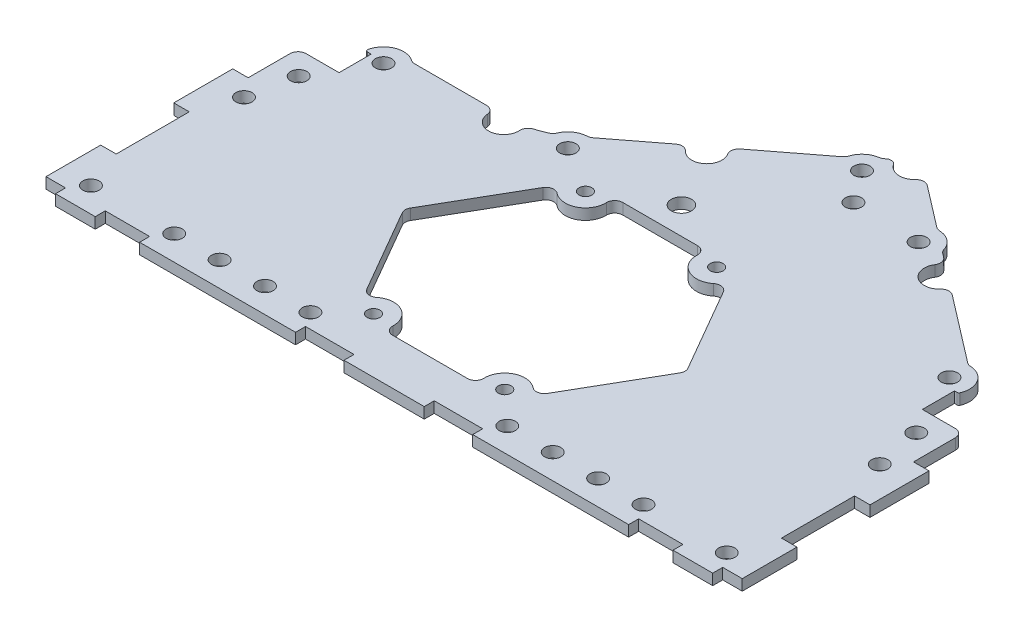
SolidWorks part; units mm, degrees
material "AISI 1020 Steel, Cold Rolled"
ref_plane "Front Plane" through (0, 0, 0) normal (0, 0, 1) x (1, 0, 0)
ref_plane "Top Plane" through (0, 0, 0) normal (0, 1, 0) x (1, 0, 0)
ref_plane "Right Plane" through (0, 0, 0) normal (1, 0, 0) x (0, 0, -1)
sketch "Top Layout" plane through (0, 0, 0) normal (0, 1, 0) x (1, 0, 0)
  line L0 (-114.046, -123.825) -> (-104.775, -123.825) construction
  line L1 (-104.775, -142.875) -> (-101.6, -142.875)
  line L2 (-104.775, -142.875) -> (-104.775, -104.775)
  line L3 (-104.775, -104.775) -> (-101.6, -104.775)
  line L4 (-101.6, -142.875) -> (-101.6, -104.775)
  line L5 (-104.775, -142.875) -> (-101.6, -104.775) construction
  line L6 (-104.775, -104.775) -> (-101.6, -142.875) construction
  line L7 (-19.05, -105.8164) -> (-101.6, -105.8164)
  line L8 (-19.05, -105.8164) -> (-19.05, -141.8336)
  line L9 (-19.05, -141.8336) -> (-101.6, -141.8336)
  line L10 (-101.6, -105.8164) -> (-101.6, -141.8336)
  line L11 (-19.05, -105.8164) -> (-101.6, -141.8336) construction
  line L12 (-19.05, -141.8336) -> (-101.6, -105.8164) construction
  line L13 (-133.096, -85.725) -> (-114.046, -85.725)
  line L14 (-133.096, -85.725) -> (-133.096, -161.925)
  line L15 (-133.096, -161.925) -> (-114.046, -161.925)
  line L16 (-114.046, -85.725) -> (-114.046, -161.925)
  line L17 (-133.096, -85.725) -> (-114.046, -161.925) construction
  line L18 (-133.096, -161.925) -> (-114.046, -85.725) construction
  line L19 (-104.775, -123.825) -> (0, -123.825) construction
  line L20 (0, -123.825) -> (0, 0) construction
  line L21 (-52.3528, -40.1717) -> (0, 0) construction
  line L22 (-70.6449, -16.3328) -> (-18.2922, 23.8388)
  line L23 (-34.0606, -64.0105) -> (18.2922, -23.8388)
  line L24 (-30.9251, 40.3023) -> (-122.2248, -29.7544)
  line L25 (-153.9748, -53.975) -> (-153.9748, -123.825)
  line L26 (-109.5248, -162.052) -> (109.5248, -162.052)
  line L27 (0, -162.052) -> (0, -123.825) construction
  line L28 (-109.5248, -162.052) -> (-109.5248, -20.0093) construction
  line L29 (-104.775, -142.875) -> (-104.775, -152.527)
  line L30 (-104.775, -152.527) -> (104.775, -152.527)
  line L31 (104.775, -104.775) -> (101.6, -104.775)
  line L32 (-144.4498, -73.025) -> (-109.5248, -73.025)
  line L33 (-144.4498, -73.025) -> (-144.4498, -123.825)
  line L34 (-144.4498, -123.825) -> (-109.5248, -123.825) construction
  line L35 (-109.5248, -73.025) -> (-109.5248, -162.052)
  line L36 (-144.4498, -73.025) -> (-109.5248, -123.825) construction
  line L37 (-144.4498, -123.825) -> (-109.5248, -73.025) construction
  line L38 (101.6, -142.875) -> (101.6, -104.775)
  line L39 (104.775, -142.875) -> (101.6, -142.875)
  line L40 (104.775, -142.875) -> (104.775, -104.775)
  line L41 (104.775, -142.875) -> (104.775, -152.527)
  line L42 (109.5248, -162.052) -> (109.5248, -20.0093) construction
  line L43 (30.9251, 40.3023) -> (122.2248, -29.7544)
  line L45 (19.05, -141.8336) -> (101.6, -141.8336)
  line L46 (101.6, -105.8164) -> (101.6, -141.8336)
  line L47 (19.05, -105.8164) -> (101.6, -105.8164)
  line L48 (19.05, -105.8164) -> (19.05, -141.8336)
  line L49 (133.096, -161.925) -> (114.046, -161.925)
  line L50 (114.046, -85.725) -> (114.046, -161.925)
  line L51 (133.096, -85.725) -> (114.046, -85.725)
  line L52 (133.096, -85.725) -> (133.096, -161.925)
  line L53 (144.4498, -123.825) -> (109.5248, -123.825) construction
  line L54 (109.5248, -73.025) -> (109.5248, -162.052)
  line L55 (144.4498, -73.025) -> (109.5248, -73.025)
  line L56 (144.4498, -73.025) -> (144.4498, -123.825)
  line L57 (-109.5248, -123.825) -> (-109.5248, -162.052) construction
  line L62 (-153.9748, -53.975) -> (-122.2248, -53.975)
  line L63 (-122.2248, -53.975) -> (-122.2248, -29.7544)
  line L64 (-144.4498, -123.825) -> (-153.9748, -123.825)
  line L65 (153.9748, -53.975) -> (153.9748, -123.825)
  line L66 (109.5248, -123.825) -> (109.5248, -162.052) construction
  line L67 (144.4498, -123.825) -> (153.9748, -123.825)
  line L68 (122.2248, -29.7544) -> (122.2248, -53.975)
  line L73 (-104.775, -104.775) -> (-104.775, -16.3647) construction
  line L74 (-95.25, -162.052) -> (-95.25, -9.0559) construction
  line L75 (-109.5248, -162.052) -> (-109.5248, -123.825) construction
  line L76 (109.5248, -162.052) -> (109.5248, -123.825) construction
  line L77 (122.2248, -53.975) -> (153.9748, -53.975)
  line L83 (104.775, -155.5496) -> (-104.775, -155.5496) construction
  line L88 (95.25, -162.052) -> (95.25, -9.0559) construction
  line L89 (104.775, -104.775) -> (104.775, -16.3647) construction
  line L92 (-104.775, -152.527) -> (-104.775, -162.052) construction
  line L93 (-14.605, -76.327) -> (14.605, -76.327)
  line L94 (-14.605, -76.327) -> (-14.605, -152.527)
  line L95 (-14.605, -152.527) -> (14.605, -152.527)
  line L96 (14.605, -76.327) -> (14.605, -152.527)
  line L97 (-14.605, -76.327) -> (14.605, -152.527) construction
  line L98 (-14.605, -152.527) -> (14.605, -76.327) construction
  line L99 (104.775, -152.527) -> (104.775, -162.052) construction
  line L100 (-19.05, -105.8164) -> (0, -105.8164) construction
  line L107 (0, -105.8164) -> (19.05, -105.8164) construction
  line L108 (104.775, -123.825) -> (114.046, -123.825) construction
  circle A0 centre (0, 0) radius 114.3
  circle A1 centre (0, 0) radius 6.35
  circle A2 centre (-52.3528, -40.1717) radius 17.8
  circle A3 centre (0, 0) radius 30.0482
  circle A4 centre (-52.3528, -40.1717) radius 30.0482
  arc A5 (-30.9251, 40.3023) -> (30.9251, 40.3023) centre (0, 0) cw
  point P2 (-103.1875, -123.825)
  point P7 (-60.325, -123.825)
  point P12 (-123.571, -123.825)
  point P30 (-126.9873, -98.425)
  point P35 (0, -114.427)
  point P53 (0, -152.527)
  dimension "D1" = 35.6
  dimension "D2" = 12.7
  dimension "D3" = 228.6
  dimension "D11" = 60.0964
  dimension "D12" = 50.8
  dimension "D14" = 52.5
  dimension "D4" = 3.175
  dimension "D5" = 19.05
  dimension "D6" = 76.2
  dimension "D7" = 82.55
  dimension "D8" = 38.1
  dimension "D9" = 104.775
  dimension "D10" = 18.0086
  dimension "D13" = 9.525
  dimension "D15" = 4.7498
  dimension "D16" = 9.525
  dimension "D17" = 9.652
  dimension "D18" = 50.8
  dimension "D19" = 12.446
  dimension "D20" = 65.9892
  dimension "D21" = 19.05
  dimension "D22" = 34.925
  dimension "D23" = 123.825
  dimension "D24" = 12.7
  dimension "D25" = 9.525
  dimension "D26" = 29.21
  dimension "D27" = 76.2
  dimension "D28" = 3.0226
sketch "Side Layout" plane through (0, 0, 0) normal (1, 0, 0) x (0, 0, -1)
  line L0 (0, -38.1) -> (0, 33.7344) construction
  line L1 (-114.3, -20.955) -> (114.3, -20.955)
  line L2 (-114.3, -20.955) -> (-114.3, -33.655)
  line L3 (-114.3, -33.655) -> (114.3, -33.655)
  line L4 (114.3, -20.955) -> (114.3, -33.655)
  line L5 (-114.3, -20.955) -> (114.3, -33.655) construction
  line L6 (-114.3, -33.655) -> (114.3, -20.955) construction
  line L7 (-9.525, -32.9406) -> (9.525, -32.9406)
  line L8 (-9.525, -32.9406) -> (-9.525, -38.1)
  line L9 (-9.525, -38.1) -> (9.525, -38.1)
  line L10 (9.525, -32.9406) -> (9.525, -38.1)
  line L11 (-9.525, -32.9406) -> (9.525, -38.1) construction
  line L12 (-9.525, -38.1) -> (9.525, -32.9406) construction
  line L13 (-11.9126, -29.3338) -> (11.9126, -29.3338)
  line L14 (-11.9126, -29.3338) -> (-11.9126, -32.9406)
  line L15 (-11.9126, -32.9406) -> (11.9126, -32.9406)
  line L16 (11.9126, -29.3338) -> (11.9126, -32.9406)
  line L17 (-11.9126, -29.3338) -> (11.9126, -32.9406) construction
  line L18 (-11.9126, -32.9406) -> (11.9126, -29.3338) construction
  line L19 (-6.35, -32.9406) -> (6.35, -32.9406)
  line L20 (-6.35, -32.9406) -> (-6.35, 33.7344)
  line L21 (-6.35, 33.7344) -> (6.35, 33.7344)
  line L22 (6.35, -32.9406) -> (6.35, 33.7344)
  line L23 (-6.35, -32.9406) -> (6.35, 33.7344) construction
  line L24 (-6.35, 33.7344) -> (6.35, -32.9406) construction
  line L25 (-162.052, 0) -> (-123.825, 0) construction
  line L26 (114.3, -33.655) -> (114.3, 0) construction
  line L27 (-142.875, 19.05) -> (-104.775, 19.05)
  line L28 (-40.1717, -9.525) -> (-40.1717, 5.4) construction
  line L29 (-142.875, 19.05) -> (-142.875, -19.05)
  line L30 (-142.875, -19.05) -> (-104.775, -19.05)
  line L31 (-104.775, 19.05) -> (-104.775, -19.05)
  line L32 (-142.875, 19.05) -> (-104.775, -19.05) construction
  line L33 (-142.875, -19.05) -> (-104.775, 19.05) construction
  line L34 (-130.175, -38.1) -> (-117.9516, -38.1) construction
  line L35 (-57.9717, -14.6) -> (-22.3717, -14.6)
  line L36 (-30.0482, -2.794) -> (30.0482, -2.794)
  line L37 (-30.0482, -2.794) -> (-30.0482, -20.955)
  line L38 (-30.0482, -20.955) -> (30.0482, -20.955)
  line L39 (30.0482, -2.794) -> (30.0482, -20.955)
  line L40 (-30.0482, -2.794) -> (30.0482, -20.955) construction
  line L41 (-30.0482, -20.955) -> (30.0482, -2.794) construction
  line L42 (-30.0482, -2.794) -> (-30.0482, 0) construction
  line L43 (-123.825, 0) -> (0, 0) construction
  line L44 (-57.9717, -14.6) -> (-57.9717, 25.4)
  line L45 (-57.9717, 25.4) -> (-22.3717, 25.4)
  line L46 (-22.3717, -14.6) -> (-22.3717, 25.4)
  line L47 (-19.05, 0) -> (19.05, 0)
  line L48 (-19.05, 0) -> (-19.05, -1.9812)
  line L49 (-19.05, -1.9812) -> (19.05, -1.9812)
  line L50 (19.05, 0) -> (19.05, -1.9812)
  line L51 (-19.05, 0) -> (19.05, -1.9812) construction
  line L52 (-19.05, -1.9812) -> (19.05, 0) construction
  line L53 (-70.2199, -3.175) -> (-10.1235, -3.175)
  line L54 (-70.2199, -3.175) -> (-70.2199, -15.875)
  line L55 (-70.2199, -15.875) -> (-10.1235, -15.875)
  line L56 (-10.1235, -3.175) -> (-10.1235, -15.875)
  line L57 (-70.2199, -3.175) -> (-10.1235, -15.875) construction
  line L58 (-70.2199, -15.875) -> (-10.1235, -3.175) construction
  line L59 (-40.1717, -9.525) -> (-40.1717, 0) construction
  line L60 (-57.9717, -14.6) -> (-22.3717, 25.4) construction
  line L61 (-57.9717, 25.4) -> (-22.3717, -14.6) construction
  line L62 (-22.3717, 0) -> (-57.9717, 0) construction
  line L63 (-137.8162, 0) -> (-123.825, -13.9912) construction
  line L64 (-139.065, 15.24) -> (-108.585, 15.24) construction
  line L65 (-139.065, 15.24) -> (-139.065, -15.24) construction
  line L66 (-139.065, -15.24) -> (-108.585, -15.24) construction
  line L67 (-108.585, 15.24) -> (-108.585, -15.24) construction
  line L68 (-139.065, 15.24) -> (-108.585, -15.24) construction
  line L69 (-139.065, -15.24) -> (-108.585, 15.24) construction
  line L70 (-137.8162, 0) -> (-123.825, 13.9912) construction
  line L71 (-123.825, -13.9912) -> (-109.8338, 0) construction
  line L72 (-123.825, 13.9912) -> (-109.8338, 0) construction
  line L73 (-137.8162, 0) -> (-109.8338, 0) construction
  line L74 (-123.825, -13.9912) -> (-123.825, 13.9912) construction
  line L75 (-6.35, 17.8594) -> (6.35, 17.8594)
  line L76 (114.3, 0) -> (-114.3, 0) construction
  line L77 (-22.3717, 19.05) -> (-6.35, 19.05) construction
  line L78 (-123.825, 38.1) -> (-97.9206, 38.1) construction
  line L79 (-19.05, -3.5814) -> (19.05, -3.5814)
  line L80 (-19.05, -3.5814) -> (-19.05, -1.9812)
  line L81 (-19.05, -1.9812) -> (19.05, -1.9812)
  line L82 (19.05, -3.5814) -> (19.05, -1.9812)
  line L83 (-19.05, -3.5814) -> (19.05, -1.9812) construction
  line L84 (-19.05, -1.9812) -> (19.05, -3.5814) construction
  line L85 (-8.7376, -16.7608) -> (8.7376, -16.7608)
  line L86 (-8.7376, -16.7608) -> (-8.7376, -29.3338)
  line L87 (-8.7376, -29.3338) -> (8.7376, -29.3338)
  line L88 (8.7376, -16.7608) -> (8.7376, -29.3338)
  line L89 (-8.7376, -16.7608) -> (8.7376, -29.3338) construction
  line L90 (-8.7376, -29.3338) -> (8.7376, -16.7608) construction
  line L91 (-8.7376, -3.5814) -> (8.7376, -3.5814)
  line L92 (-8.7376, -3.5814) -> (-8.7376, -16.1544)
  line L93 (-8.7376, -16.1544) -> (8.7376, -16.1544)
  line L94 (8.7376, -3.5814) -> (8.7376, -16.1544)
  line L95 (-8.7376, -3.5814) -> (8.7376, -16.1544) construction
  line L96 (-8.7376, -16.1544) -> (8.7376, -3.5814) construction
  circle A0 centre (-123.825, 0) radius 18.0086
  circle A1 centre (-123.825, 0) radius 38.1
  circle A2 centre (-139.065, 15.24) radius 1.905
  circle A3 centre (-108.585, 15.24) radius 1.905
  circle A4 centre (-108.585, -15.24) radius 1.905
  circle A5 centre (-139.065, -15.24) radius 1.905
  circle A6 centre (-137.8162, 0) radius 1.6002
  circle A7 centre (-123.825, 13.9912) radius 1.6002
  circle A8 centre (-109.8338, 0) radius 1.6002
  circle A9 centre (-123.825, -13.9912) radius 1.6002
  point P0 (0, -27.305)
  point P6 (0, -31.1372)
  point P7 (0, -35.5203)
  point P21 (0, 0.3969)
  point P32 (0, -11.8745)
  point P43 (0, -0.9906)
  point P55 (-40.1717, -9.525)
  point P72 (-40.1717, 5.4)
  point P88 (0, -23.0473)
  point P93 (0, -2.7813)
  point P102 (0, -9.8679)
  dimension "D17" = 3.81
  dimension "D18" = 3.2004
  dimension "D1" = 12.7
  dimension "D2" = 5.1594
  dimension "D3" = 19.05
  dimension "D4" = 3.6068
  dimension "D5" = 23.8252
  dimension "D6" = 12.7
  dimension "D7" = 18.161
  dimension "D8" = 1.9812
  dimension "D9" = 12.7
  dimension "D10" = 40
  dimension "D11" = 25.4
  dimension "D12" = 50.8
  dimension "D13" = 41.275
  dimension "D14" = 30.48
  dimension "D15" = 4.445
  dimension "D16" = 19.7866
  dimension "D19" = 15.875
  dimension "D20" = 6.35
  dimension "D21" = 38.1
  dimension "D22" = 1.6002
  dimension "D23" = 38.1
  dimension "D24" = 17.4752
  dimension "D25" = 12.573
ref_plane "Plane1" through (0, 25.4, 0) normal (0, 1, 0) x (1, 0, 0)
sketch "Sketch3" plane through (0, 25.4, 0) normal (0, 1, 0) x (1, 0, 0)
  line L0 (-104.775, -36.3747) -> (-30.9251, 20.2924)
  line L1 (-104.775, -104.775) -> (-104.775, -16.3647) construction
  line L2 (0, -200130.175) -> (0, 199882.0484) construction
  line L3 (-30.9251, 40.3023) -> (-122.2248, -29.7544) construction
  line L5 (-104.775, -36.3747) -> (-104.775, -77.6497)
  line L6 (-92.075, -77.6497) -> (-104.775, -77.6497)
  line L7 (30.9251, 20.2924) -> (104.775, -36.3747)
  line L8 (104.775, -77.6497) -> (92.075, -77.6497)
  line L9 (104.775, -36.3747) -> (104.775, -77.6497)
  line L11 (104.775, -104.775) -> (104.775, -16.3647) construction
  line L12 (30.9251, 40.3023) -> (122.2248, -29.7544) construction
  line L13 (92.075, -74.6536) -> (24.1423, -22.5271)
  line L14 (-32.2514, -66.3682) -> (20.1013, -26.1965)
  line L15 (-30.9251, 20.2924) -> (0, 44.022)
  line L16 (0, 44.022) -> (30.9251, 20.2924)
  line L17 (-92.075, -77.6497) -> (-92.075, -73.1917)
  line L19 (-92.075, -73.1917) -> (-52.3528, -73.1917)
  line L20 (92.075, -74.6536) -> (92.075, -77.6497)
  circle A0 centre (-52.3528, -40.1717) radius 17.8 construction
  circle A1 centre (-52.3528, -40.1717) radius 17.8
  circle A2 centre (0, 0) radius 6.35
  circle A3 centre (0, 0) radius 6.35 construction
  arc A4 (-52.3528, -73.1917) -> (-32.2514, -66.3682) centre (-52.3528, -40.1717) ccw
  arc A5 (20.1013, -26.1965) -> (24.1423, -22.5271) centre (0, 0) ccw
  arc A6 (30.9251, 20.2924) -> (-30.9251, 20.2924) centre (0, -20.01) ccw construction
  point P28 (0, 44.022)
  dimension "D1" = 33.02
  dimension "D5" = 50.8
  dimension "D2" = 41.275
  dimension "D3" = 34.925
  dimension "D4" = 12.7
  dimension "D6" = 38.1
ref_plane "Plane3" through (-104.775, 0, 0) normal (-1, 0, 0) x (0, 0, 1)
sketch "Sketch6" plane through (-104.775, 0, 0) normal (-1, 0, 0) x (0, 0, 1)
  line L0 (162.052, -25.4) -> (162.052, 25.4)
  line L1 (162.052, 25.4) -> (77.6497, 25.4)
  line L2 (36.3747, 25.4) -> (77.6497, 25.4) construction
  line L3 (147.7645, 11.1125) -> (162.052, 11.1125) construction
  line L4 (162.052, 0) -> (71.2997, 0) construction
  line L5 (77.6497, 25.4) -> (77.6497, 19.05)
  line L6 (77.6497, 19.05) -> (36.3747, 19.05)
  line L7 (36.3747, 19.05) -> (36.3747, 6.35)
  line L8 (36.3747, 6.35) -> (71.2997, 6.35)
  line L10 (99.6315, -3.175) -> (99.6315, 11.1125) construction
  line L11 (71.2997, -25.4) -> (162.052, -25.4)
  line L13 (71.2997, 6.35) -> (71.2997, -25.4)
  line L14 (152.527, -25.4) -> (152.527, 25.4) construction
  line L15 (99.6315, 11.1125) -> (99.6315, 25.4) construction
  line L16 (147.7645, 11.1125) -> (147.7645, 25.4) construction
  line L17 (94.869, -7.9375) -> (104.394, -7.9375) construction
  line L18 (94.869, -7.9375) -> (94.869, 25.4) construction
  line L19 (94.869, 25.4) -> (104.394, 25.4) construction
  line L20 (104.394, -7.9375) -> (104.394, 25.4) construction
  line L21 (94.869, -7.9375) -> (104.394, 25.4) construction
  line L22 (94.869, 25.4) -> (104.394, -7.9375) construction
  line L23 (147.7645, 11.1125) -> (147.7645, -3.175) construction
  line L24 (104.394, -7.9375) -> (123.825, -7.9375) construction
  line L25 (143.002, -7.9375) -> (152.527, -7.9375) construction
  line L26 (143.002, -7.9375) -> (143.002, 25.4) construction
  line L27 (143.002, 25.4) -> (152.527, 25.4) construction
  line L28 (152.527, -7.9375) -> (152.527, 25.4) construction
  line L29 (143.002, -7.9375) -> (152.527, 25.4) construction
  line L30 (143.002, 25.4) -> (152.527, -7.9375) construction
  line L31 (123.825, -7.9375) -> (152.527, -7.9375) construction
  line L32 (104.775, 19.05) -> (104.775, -19.05) construction
  line L34 (155.702, -25.4) -> (155.702, 25.4) construction
  circle A0 centre (109.8338, 0) radius 1.6002 construction
  circle A1 centre (123.825, 13.9912) radius 1.6002 construction
  circle A2 centre (137.8162, 0) radius 1.6002 construction
  circle A3 centre (123.825, -13.9912) radius 1.6002 construction
  circle A4 centre (109.8338, 0) radius 1.6002 construction
  circle A5 centre (123.825, 13.9912) radius 1.6002 construction
  circle A6 centre (137.8162, 0) radius 1.6002 construction
  circle A7 centre (123.825, -13.9912) radius 1.6002 construction
  circle A8 centre (123.825, 0) radius 18.0086 construction
  circle A9 centre (123.825, 0) radius 18.0086 construction
  circle A10 centre (123.825, 0) radius 9.525
  circle A11 centre (108.585, -15.24) radius 1.905 construction
  circle A12 centre (108.585, 15.24) radius 1.905 construction
  circle A13 centre (139.065, 15.24) radius 1.905 construction
  circle A14 centre (139.065, -15.24) radius 1.905 construction
  circle A15 centre (108.585, -15.24) radius 1.905
  circle A16 centre (108.585, 15.24) radius 1.905
  circle A17 centre (139.065, 15.24) radius 1.905
  circle A18 centre (139.065, -15.24) radius 1.905
  circle A19 centre (147.7645, 11.1125) radius 2.5527
  circle A26 centre (99.6315, 11.1125) radius 2.5527
  circle A27 centre (99.6315, -3.175) radius 2.5527
  circle A28 centre (147.7645, -3.175) radius 2.5527
  point P29 (0, 0)
  point P55 (99.6315, 8.7312)
  point P61 (147.7645, 8.7312)
  dimension "D4" = 19.05
  dimension "D7" = 5.1054
  dimension "D1" = 6.35
  dimension "D2" = 12.7
  dimension "D3" = 25.4
  dimension "D5" = 6.35
  dimension "D6" = 3.175
  dimension "D8" = 0.381
  dimension "D9" = 14.2875
  dimension "D10" = 9.525
  dimension "D12" = 33.3375
ref_plane "Plane4" through (0, 19.05, 0) normal (0, 1, 0) x (1, 0, 0)
sketch "Sketch12" plane through (0, 19.05, 0) normal (0, 1, 0) x (1, 0, 0)
  line L0 (-104.775, -77.6497) -> (-104.775, -36.3747)
  line L1 (-104.775, -36.3747) -> (-92.075, -36.3747)
  line L3 (-92.075, -36.3747) -> (-92.075, -77.6497)
  line L5 (-92.075, -77.6497) -> (-104.775, -77.6497)
  line L6 (-98.425, -77.6497) -> (-98.425, -63.3622) construction
  line L7 (-98.425, -63.3622) -> (-98.425, -50.6622) construction
  line L8 (-98.425, -50.6622) -> (-98.425, -36.3747) construction
  line L10 (-98.425, -36.3747) -> (-104.775, -36.3747) construction
  circle A0 centre (-98.425, -63.3622) radius 2.5527
  circle A1 centre (-98.425, -50.6622) radius 2.5527
  dimension "D2" = 5.1054
  dimension "D1" = 12.7
  dimension "D3" = 12.7
sketch "Sketch25" plane through (0, 25.4, 0) normal (0, 1, 0) x (1, 0, 0)
  line L0 (-104.775, -152.527) -> (104.775, -152.527)
  line L1 (-104.775, -152.527) -> (104.775, -152.527) construction
  line L2 (104.775, -152.527) -> (104.775, -162.052)
  line L3 (104.775, -162.052) -> (-104.775, -162.052)
  line L4 (-104.775, -162.052) -> (-104.775, -152.527)
ref_plane "Plane5" through (0, 0, 152.527) normal (0, 0, 1) x (1, 0, 0)
sketch "Sketch41" plane through (0, 0, 152.527) normal (0, 0, 1) x (1, 0, 0)
  line L0 (-104.775, -7.9375) -> (-104.775, 25.4) construction
  line L1 (-104.775, -7.9375) -> (-104.775, 12.7)
  line L2 (-104.775, -7.9375) -> (104.775, -7.9375)
  line L3 (104.775, -7.9375) -> (104.775, 12.7)
  line L4 (104.775, 25.4) -> (-104.775, 25.4)
  line L5 (0, -7.9375) -> (0, 25.4) construction
  line L6 (-104.775, 3.9624) -> (-100.0125, 3.9624) construction
  line L7 (-100.0125, 3.9624) -> (-100.0125, 25.4) construction
  line L8 (104.775, 3.9624) -> (100.0125, 3.9624) construction
  line L9 (100.0125, 3.9624) -> (100.0125, 25.4) construction
  line L10 (19.05, 20.6375) -> (23.8252, 20.6375) construction
  line L11 (19.05, 15.875) -> (78.5876, 15.875) construction
  line L12 (19.05, 15.875) -> (19.05, 25.4) construction
  line L13 (19.05, 25.4) -> (78.5876, 25.4) construction
  line L14 (78.5876, 15.875) -> (78.5876, 25.4) construction
  line L15 (19.05, 15.875) -> (78.5876, 25.4) construction
  line L16 (19.05, 25.4) -> (78.5876, 15.875) construction
  line L17 (23.8252, 20.6375) -> (38.1127, 20.6375) construction
  line L18 (38.1127, 20.6375) -> (52.4002, 20.6375) construction
  line L19 (52.4002, 20.6375) -> (66.6877, 20.6375) construction
  line L20 (-104.775, 25.4) -> (-112.395, 25.4)
  line L21 (-112.395, 25.4) -> (-112.395, 3.175)
  line L22 (-112.395, 3.175) -> (-109.5248, 3.175)
  line L23 (-109.5248, 3.175) -> (-109.5248, 12.7)
  line L24 (-109.5248, 12.7) -> (-104.775, 12.7)
  line L25 (-104.775, 12.7) -> (-104.775, 25.4) construction
  line L26 (104.775, 25.4) -> (112.395, 25.4)
  line L27 (112.395, 25.4) -> (112.395, 3.175)
  line L28 (112.395, 3.175) -> (109.5248, 3.175)
  line L29 (109.5248, 3.175) -> (109.5248, 12.7)
  line L30 (109.5248, 12.7) -> (104.775, 12.7)
  line L31 (104.775, 12.7) -> (104.775, 25.4) construction
  line L32 (-100.0125, 3.9624) -> (-87.3125, 3.9624) construction
  line L33 (-63.5, -1.5875) -> (0, -1.5875) construction
  line L34 (0, -1.5875) -> (63.5, -1.5875) construction
  line L35 (63.5, -1.5875) -> (63.5, -7.9375) construction
  circle A0 centre (-100.0125, 3.9624) radius 2.5527
  circle A1 centre (100.0125, 3.9624) radius 2.5527
  circle A2 centre (23.8252, 20.6375) radius 2.5527
  circle A3 centre (38.1127, 20.6375) radius 2.5527
  circle A4 centre (52.4002, 20.6375) radius 2.5527
  circle A5 centre (66.6877, 20.6375) radius 2.5527
  circle A6 centre (-66.6877, 20.6375) radius 2.5527
  circle A7 centre (-52.4002, 20.6375) radius 2.5527
  circle A8 centre (-38.1127, 20.6375) radius 2.5527
  circle A9 centre (-23.8252, 20.6375) radius 2.5527
  circle A10 centre (-87.3125, 3.9624) radius 2.5527
  circle A11 centre (87.3125, 3.9624) radius 2.5527
  circle A12 centre (-63.5, -1.5875) radius 2.5527
  circle A13 centre (63.5, -1.5875) radius 2.5527
  point P14 (48.8188, 20.6375)
  dimension "D3" = 5.1054
  dimension "D7" = 5.1054
  dimension "D1" = 21.4376
  dimension "D2" = 4.7625
  dimension "D4" = 9.525
  dimension "D5" = 59.5376
  dimension "D6" = 4.7752
  dimension "D8" = 14.2875
  dimension "D9" = 7.62
  dimension "D10" = 4.7498
  dimension "D11" = 12.7
  dimension "D12" = 9.525
  dimension "D13" = 19.05
  dimension "D14" = 12.7
  dimension "D15" = 6.35
  dimension "D16" = 63.5
sketch "Sketch44" plane through (0, 25.4, 0) normal (0, 1, 0) x (1, 0, 0)
  line L0 (73.8315, -147.7645) -> (73.8315, -152.527) construction
  line L1 (92.075, -74.6536) -> (92.075, -77.6497) construction
  line L2 (-92.075, -77.6497) -> (-92.075, -73.1917) construction
  line L3 (0, -123.825) -> (0, 0) construction
  line L4 (-92.075, -73.1917) -> (-52.3528, -73.1917) construction
  line L5 (-104.775, -104.775) -> (-104.775, -16.3647) construction
  line L6 (-32.2514, -66.3682) -> (20.1013, -26.1965) construction
  line L21 (-104.775, -68.1247) -> (-104.775, -152.527)
  line L22 (-104.775, -152.527) -> (104.775, -152.527)
  line L23 (104.775, -152.527) -> (104.775, -68.1247)
  line L34 (-104.775, -99.6315) -> (-100.0125, -99.6315) construction
  line L35 (-104.775, -147.7645) -> (-100.0125, -147.7645) construction
  line L36 (0, -152.527) -> (0, -35.6178) construction
  line L38 (30.969, -147.7645) -> (45.2565, -147.7645) construction
  line L39 (45.2565, -147.7645) -> (59.544, -147.7645) construction
  line L40 (59.544, -147.7645) -> (73.8315, -147.7645) construction
  line L41 (23.8252, -152.527) -> (30.969, -152.527) construction
  line L42 (104.775, -152.527) -> (-104.775, -152.527) construction
  line L43 (30.969, -152.527) -> (38.1127, -152.527) construction
  line L44 (30.969, -152.527) -> (30.969, -147.7645) construction
  line L45 (-92.075, -77.6497) -> (-104.775, -77.6497) construction
  line L48 (-35.1507, -62.5899) -> (-8.9743, -42.504) construction
  line L49 (-8.9743, -42.504) -> (17.2021, -22.4182) construction
  line L50 (45.5313, -32.9364) -> (87.3125, -64.9962) construction
  line L51 (92.075, -74.6536) -> (24.1423, -22.5271) construction
  line L52 (104.775, -77.6497) -> (92.075, -77.6497) construction
  line L79 (-104.775, -68.1247) -> (-92.075, -68.1247)
  line L80 (-92.075, -68.1247) -> (-92.075, -63.6667)
  line L85 (21.8118, -8.7328) -> (92.075, -62.6476)
  line L86 (-38.0499, -58.8115) -> (14.3028, -18.6398)
  line L87 (-92.075, -63.6667) -> (-52.3528, -63.6667)
  line L88 (92.075, -62.6476) -> (92.075, -68.1247)
  line L89 (92.075, -68.1247) -> (104.775, -68.1247)
  circle A0 centre (-73.8315, -147.7645) radius 2.5527
  circle A1 centre (-59.544, -147.7645) radius 2.5527
  circle A2 centre (-45.2565, -147.7645) radius 2.5527
  circle A3 centre (-30.969, -147.7645) radius 2.5527
  circle A17 centre (-100.0125, -99.6315) radius 2.5527
  circle A18 centre (-100.0125, -147.7645) radius 2.5527
  circle A19 centre (100.0125, -147.7645) radius 2.5527
  circle A20 centre (100.0125, -99.6315) radius 2.5527
  circle A21 centre (30.969, -147.7645) radius 2.5527
  circle A22 centre (45.2565, -147.7645) radius 2.5527
  circle A23 centre (59.544, -147.7645) radius 2.5527
  circle A24 centre (73.8315, -147.7645) radius 2.5527
  circle A25 centre (-87.3125, -68.4292) radius 4.7625 construction
  circle A26 centre (-35.1507, -62.5899) radius 4.7625 construction
  circle A27 centre (-8.9743, -42.504) radius 4.7625 construction
  circle A28 centre (17.2021, -22.4182) radius 4.7625 construction
  circle A29 centre (45.5313, -32.9364) radius 4.7625 construction
  circle A30 centre (87.3125, -64.9962) radius 4.7625 construction
  circle A32 centre (-87.3125, -68.4292) radius 2.5527
  circle A33 centre (-35.1507, -62.5899) radius 2.5527
  circle A34 centre (-8.9743, -42.504) radius 2.5527 construction
  circle A35 centre (17.2021, -22.4182) radius 2.5527
  circle A36 centre (45.5313, -32.9364) radius 2.5527
  circle A37 centre (87.3125, -64.9962) radius 2.5527
  circle A38 centre (-97.155, -85.2697) radius 7.62 construction
  circle A39 centre (97.155, -85.2697) radius 7.62 construction
  circle A40 centre (24.5121, -32.4156) radius 7.62 construction
  arc A41 (20.1013, -26.1965) -> (24.1423, -22.5271) centre (0, 0) ccw construction
  circle A42 centre (-97.155, -85.2697) radius 2.5527
  circle A43 centre (24.5121, -32.4156) radius 2.5527
  circle A44 centre (97.155, -85.2697) radius 2.5527
  arc A56 (14.3028, -18.6398) -> (21.8118, -8.7328) centre (0, 0) ccw
  arc A57 (-52.3528, -63.6667) -> (-38.0499, -58.8115) centre (-52.3528, -40.1717) ccw
  point P4 (-104.775, -152.527)
  dimension "D2" = 5.1054
  dimension "D7" = 5.1054
  dimension "D8" = 15.24
  dimension "D3" = 9.525
  dimension "D9" = 9.525
  dimension "D4" = 4.7625
  dimension "D5" = 14.2875
  dimension "D6" = 9.525
  dimension "D1" = 4.7625
  dimension "D10" = 52.664
extrude "Top Plate Extrude-----------" add sketch "Sketch44" along normal blind 3.429
sketch "Sketch82" plane through (0, 28.829, 0) normal (0, 1, 0) x (1, 0, 0)
  line L0 (-52.3528, -63.6667) -> (-92.075, -63.6667) construction
  line L1 (-52.3528, -65.5717) -> (-52.3528, -63.6667) construction
  line L2 (-12.4467, -41.5667) -> (-13.6064, -40.0553) construction
  line L3 (14.3028, -18.6398) -> (-38.0499, -58.8115) construction
  line L4 (24.5175, -13.2101) -> (25.6772, -11.6988) construction
  line L5 (92.075, -62.6476) -> (21.8118, -8.7328) construction
  line L6 (58.2962, -39.1295) -> (59.4559, -37.6181) construction
  line L7 (21.4643, -9.5551) -> (21.8118, -8.7328)
  line L8 (21.8118, -8.7328) -> (22.2143, -9.0416)
  circle A0 centre (-52.3528, -65.5717) radius 4.7625
  circle A1 centre (-12.4467, -41.5667) radius 4.7625
  arc A2 (21.4643, -9.5551) -> (22.2143, -9.0416) centre (24.5175, -13.2101) ccw
  circle A3 centre (58.2962, -39.1295) radius 4.7625
  arc A4 (14.3028, -18.6398) -> (21.8118, -8.7328) centre (0, 0) ccw construction
  dimension "D1" = 9.525
  dimension "D2" = 1.905
  dimension "D3" = 30.8104
  dimension "D4" = 83.6926
  dimension "D5" = 41.1154
extrude "Cut-Extrude38" cut sketch "Sketch82" against normal up to surface (3.429 mm away) up to face at (-4.435, 25.4, 71.2837)
sketch "Sketch72" plane through (0, 25.4, 0) normal (0, 1, 0) x (1, 0, 0)
  line L0 (-104.775, -68.1247) -> (-104.775, -152.527) construction
  line L1 (-104.775, -152.527) -> (-109.5248, -152.527)
  line L2 (-104.775, -152.527) -> (-104.775, -135.0645)
  line L3 (-104.775, -135.0645) -> (-109.5248, -135.0645)
  line L4 (-109.5248, -152.527) -> (-109.5248, -135.0645)
  line L5 (-104.775, -152.527) -> (-109.5248, -135.0645) construction
  line L6 (-104.775, -135.0645) -> (-109.5248, -152.527) construction
  line L7 (-104.775, -152.527) -> (104.775, -152.527) construction
  line L8 (-77.0065, -152.527) -> (-73.8315, -147.7645) construction
  line L9 (-77.0065, -152.527) -> (-27.794, -152.527)
  line L10 (-77.0065, -152.527) -> (-77.0065, -155.5496)
  line L11 (-77.0065, -155.5496) -> (-27.794, -155.5496)
  line L12 (-27.794, -152.527) -> (-27.794, -155.5496)
  line L13 (-77.0065, -152.527) -> (-27.794, -155.5496) construction
  line L14 (-77.0065, -155.5496) -> (-27.794, -152.527) construction
  line L15 (-27.794, -152.527) -> (-30.969, -147.7645) construction
  line L16 (-77.0065, -152.527) -> (-77.0065, -147.7645) construction
  line L18 (-104.775, -93.5247) -> (-109.5248, -93.5247)
  line L19 (-104.775, -93.5247) -> (-104.775, -112.3315)
  line L20 (-104.775, -112.3315) -> (-109.5248, -112.3315)
  line L21 (-109.5248, -93.5247) -> (-109.5248, -112.3315)
  line L22 (-104.775, -93.5247) -> (-109.5248, -112.3315) construction
  line L23 (-104.775, -112.3315) -> (-109.5248, -93.5247) construction
  line L24 (0, -152.527) -> (-12.7, -152.527)
  line L25 (0, -152.527) -> (0, -155.5496)
  line L26 (0, -155.5496) -> (-12.7, -155.5496)
  line L27 (-12.7, -152.527) -> (-12.7, -155.5496)
  line L28 (0, -152.527) -> (-12.7, -155.5496) construction
  line L29 (0, -155.5496) -> (-12.7, -152.527) construction
  line L30 (-104.775, -68.1247) -> (-109.5248, -68.1247)
  line L31 (-104.775, -68.1247) -> (-104.775, -77.6497)
  line L32 (-104.775, -77.6497) -> (-109.5248, -77.6497)
  line L33 (-109.5248, -68.1247) -> (-109.5248, -77.6497)
  line L34 (-104.775, -68.1247) -> (-109.5248, -77.6497) construction
  line L35 (-104.775, -77.6497) -> (-109.5248, -68.1247) construction
  line L38 (-103.505, -155.5496) -> (-90.805, -155.5496)
  line L39 (-90.805, -152.527) -> (-90.805, -155.5496)
  line L40 (-103.505, -155.5496) -> (-103.505, -152.527)
  line L41 (-103.505, -155.5496) -> (-90.805, -152.527) construction
  line L42 (-103.505, -152.527) -> (-90.805, -152.527)
  line L43 (-77.0065, -147.7645) -> (-73.8315, -147.7645) construction
  line L44 (-103.505, -152.527) -> (-101.5221, -149.823) construction
  circle A0 centre (-100.0125, -147.7645) radius 2.5527 construction
  circle A1 centre (-73.8315, -147.7645) radius 2.5527 construction
  circle A2 centre (-30.969, -147.7645) radius 2.5527 construction
  point P4 (-107.1499, -143.7958)
  point P5 (-100.0125, -147.7645)
  point P16 (-52.4002, -154.0383)
  point P18 (-97.155, -154.0383)
  point P25 (-107.1499, -102.9281)
  point P34 (-6.35, -154.0383)
  point P39 (-107.1499, -72.8872)
  dimension "D1" = 4.7498
  dimension "D2" = 12.7
  dimension "D3" = 12.7
  dimension "D4" = 12.7
  dimension "D5" = 9.525
  dimension "D6" = 15.875
  dimension "D7" = 12.7
  dimension "D8" = 3.175
  dimension "D9" = 1.27
  dimension "D10" = 3.0226
extrude "Boss-Extrude27" add sketch "Sketch72" along normal through all
mirror "Mirror22" about plane through (0, 0, 0) normal (1, 0, 0) of "Boss-Extrude27"
sketch "Sketch86" plane through (0, 28.829, 0) normal (0, 1, 0) x (1, 0, 0)
  circle A0 centre (87.3125, -64.9962) radius 6.35
  circle A3 centre (17.2021, -22.4182) radius 6.35
  circle A4 centre (45.5313, -32.9364) radius 6.35
  circle A5 centre (-35.1507, -62.5899) radius 6.35
  circle A6 centre (-87.3125, -68.4292) radius 6.35
  circle A7 centre (87.3125, -64.9962) radius 2.5527 construction
  circle A8 centre (45.5313, -32.9364) radius 2.5527 construction
  circle A9 centre (17.2021, -22.4182) radius 2.5527 construction
  circle A10 centre (-35.1507, -62.5899) radius 2.5527 construction
  circle A11 centre (-87.3125, -68.4292) radius 2.5527 construction
  circle A12 centre (87.3125, -64.9962) radius 2.5527
  circle A13 centre (45.5313, -32.9364) radius 2.5527
  circle A14 centre (17.2021, -22.4182) radius 2.5527
  circle A15 centre (-35.1507, -62.5899) radius 2.5527
  circle A16 centre (-87.3125, -68.4292) radius 2.5527
  dimension "D1" = 12.7
extrude "Boss-Extrude31" add sketch "Sketch86" against normal through all
ref_plane "Plane8" through (0, 28.829, 0) normal (0, 1, 0) x (1, 0, 0)
sketch "Sketch87" plane through (0, 28.829, 0) normal (0, 1, 0) x (1, 0, 0)
  line L0 (0, -123.825) -> (0, 0) construction
  line L1 (-25.4, -66.802) -> (25.4, -66.802)
  line L2 (-25.4, -66.802) -> (-25.4, -143.002) construction
  line L3 (-25.4, -143.002) -> (25.4, -143.002)
  line L4 (25.4, -66.802) -> (25.4, -143.002) construction
  line L5 (-25.4, -66.802) -> (25.4, -143.002) construction
  line L6 (-25.4, -143.002) -> (25.4, -66.802) construction
  line L7 (-104.775, -152.527) -> (104.775, -152.527) construction
  line L8 (-25.4, -71.5645) -> (-20.6375, -71.5645) construction
  line L9 (-20.6375, -71.5645) -> (-20.6375, -66.802) construction
  line L10 (20.6375, -66.802) -> (20.6375, -71.5645) construction
  line L11 (20.6375, -71.5645) -> (25.4, -71.5645) construction
  line L12 (20.6375, -143.002) -> (20.6375, -138.2395) construction
  line L13 (20.6375, -138.2395) -> (25.4, -138.2395) construction
  line L14 (-20.6375, -143.002) -> (-20.6375, -138.2395) construction
  line L15 (-20.6375, -138.2395) -> (-25.4, -138.2395) construction
  line L16 (-25.4, -143.002) -> (-47.397, -104.902)
  line L17 (-47.397, -104.902) -> (-25.4, -66.802)
  line L18 (25.4, -66.802) -> (47.397, -104.902)
  line L19 (47.397, -104.902) -> (25.4, -143.002)
  circle A0 centre (-20.6375, -71.5645) radius 2.5527
  circle A1 centre (20.6375, -71.5645) radius 2.5527
  circle A3 centre (-20.6375, -138.2395) radius 2.5527
  circle A4 centre (20.6375, -138.2395) radius 2.5527
  point P0 (0, -104.902)
  dimension "D5" = 5.1054
  dimension "D1" = 50.8
  dimension "D2" = 9.525
  dimension "D3" = 76.2
  dimension "D4" = 4.7625
  dimension "D6" = 120
sketch "Sketch111" plane through (0, 28.829, 0) normal (0, 1, 0) x (1, 0, 0)
  line L0 (-109.5248, -77.6497) -> (-104.775, -77.6497) construction
  line L1 (-109.5248, -67.8707) -> (-91.7575, -67.8707)
  line L2 (-109.5248, -67.8707) -> (-109.5248, -77.9672)
  line L3 (-109.5248, -77.9672) -> (-91.7575, -77.9672)
  line L4 (-91.7575, -67.8707) -> (-91.7575, -77.9672)
  line L5 (-109.5248, -67.8707) -> (-91.7575, -77.9672) construction
  line L6 (-109.5248, -77.9672) -> (-91.7575, -67.8707) construction
  line L7 (109.5248, -67.8707) -> (91.7575, -67.8707)
  line L8 (109.5248, -67.8707) -> (109.5248, -77.9672)
  line L9 (109.5248, -77.9672) -> (91.7575, -77.9672)
  line L10 (91.7575, -67.8707) -> (91.7575, -77.9672)
  line L11 (109.5248, -67.8707) -> (91.7575, -77.9672) construction
  line L12 (109.5248, -77.9672) -> (91.7575, -67.8707) construction
  line L13 (-93.6552, -68.1247) -> (-109.5248, -68.1247) construction
  line L14 (-109.5248, -68.1247) -> (-109.5248, -77.6497) construction
  line L15 (109.5248, -68.1247) -> (109.5248, -77.6497) construction
  line L16 (-104.775, -104.775) -> (-104.775, -16.3647) construction
  point P4 (-100.6411, -72.9189)
  point P10 (100.6411, -72.9189)
  dimension "D1" = 13.0175
  dimension "D2" = 0.3175
  dimension "D3" = 0.254
extrude "Cut-Extrude57" cut sketch "Sketch111" against normal through all
sketch "Sketch92" plane through (0, 28.829, 0) normal (0, 1, 0) x (1, 0, 0)
  line L0 (-109.5248, -93.5247) -> (-109.5248, -112.3315) construction
  line L1 (-109.5248, -93.6517) -> (-104.665, -93.6517)
  line L2 (-109.5248, -93.6517) -> (-109.5248, -77.9672)
  line L3 (-109.5248, -77.9672) -> (-104.665, -77.9672)
  line L4 (-104.665, -93.6517) -> (-104.665, -77.9672)
  line L5 (-109.5248, -93.6517) -> (-104.665, -77.9672) construction
  line L6 (-109.5248, -77.9672) -> (-104.665, -93.6517) construction
  line L7 (-109.5248, -135.0645) -> (-109.5248, -152.527) construction
  line L8 (-109.5248, -135.1915) -> (-104.648, -135.1915)
  line L9 (-109.5248, -135.1915) -> (-109.5248, -112.2045)
  line L10 (-109.5248, -112.2045) -> (-104.648, -112.2045)
  line L11 (-104.648, -135.1915) -> (-104.648, -112.2045)
  line L12 (-109.5248, -135.1915) -> (-104.648, -112.2045) construction
  line L13 (-109.5248, -112.2045) -> (-104.648, -135.1915) construction
  line L14 (-103.505, -155.5496) -> (-90.805, -155.5496) construction
  line L15 (-103.378, -155.5496) -> (-109.5248, -155.5496)
  line L16 (-103.378, -155.5496) -> (-103.378, -152.4)
  line L17 (-103.378, -152.4) -> (-109.5248, -152.4)
  line L18 (-109.5248, -155.5496) -> (-109.5248, -152.4)
  line L19 (-103.378, -155.5496) -> (-109.5248, -152.4) construction
  line L20 (-103.378, -152.4) -> (-109.5248, -155.5496) construction
  line L21 (-77.0065, -155.5496) -> (-27.794, -155.5496) construction
  line L22 (-90.8812, -155.5496) -> (-76.9302, -155.5496)
  line L23 (-90.8812, -155.5496) -> (-90.8812, -152.4)
  line L24 (-90.8812, -152.4) -> (-76.9302, -152.4)
  line L25 (-76.9302, -155.5496) -> (-76.9302, -152.4)
  line L26 (-90.8812, -155.5496) -> (-76.9302, -152.4) construction
  line L27 (-90.8812, -152.4) -> (-76.9302, -155.5496) construction
  line L28 (-27.8702, -155.5496) -> (-12.6238, -155.5496)
  line L29 (-27.8702, -155.5496) -> (-27.8702, -152.4)
  line L30 (-27.8702, -152.4) -> (-12.6238, -152.4)
  line L31 (-12.6238, -155.5496) -> (-12.6238, -152.4)
  line L32 (-27.8702, -155.5496) -> (-12.6238, -152.4) construction
  line L33 (-27.8702, -152.4) -> (-12.6238, -155.5496) construction
  line L34 (-104.775, -77.9672) -> (-91.7575, -77.9672) construction
  line L35 (-104.775, -85.7459) -> (-104.665, -85.8094) construction
  line L36 (-104.775, -77.9672) -> (-104.775, -93.5247) construction
  line L37 (-104.775, -93.5247) -> (-104.775, -93.6517) construction
  line L38 (-104.775, -112.3315) -> (-104.775, -112.2045) construction
  line L39 (-104.775, -123.698) -> (-104.648, -123.698) construction
  line L40 (-104.775, -112.3315) -> (-104.775, -135.0645) construction
  line L41 (-104.775, -135.0645) -> (-104.775, -135.1915) construction
  line L42 (-103.505, -152.527) -> (-103.505, -152.4) construction
  line L43 (-103.505, -152.527) -> (-103.378, -152.527) construction
  line L44 (-90.8812, -152.527) -> (-90.805, -152.527) construction
  line L45 (-83.9057, -152.527) -> (-83.9057, -152.4) construction
  line L46 (-90.805, -152.527) -> (-77.0065, -152.527) construction
  line L47 (-77.0065, -152.527) -> (-76.9302, -152.527) construction
  line L48 (-27.794, -152.527) -> (-27.8702, -152.527) construction
  line L49 (-20.247, -152.527) -> (-20.247, -152.4) construction
  line L50 (-27.794, -152.527) -> (-12.7, -152.527) construction
  line L51 (-12.7, -152.527) -> (-12.6238, -152.527) construction
  line L52 (-12.7, -155.5496) -> (12.7, -155.5496) construction
  point P4 (-107.0949, -85.8094)
  point P11 (-107.0864, -123.698)
  point P18 (-106.4514, -153.9748)
  point P25 (-83.9057, -153.9748)
  point P30 (-20.247, -153.9748)
  dimension "D1" = 0.0762
  dimension "D2" = 0.127
extrude "Cut-Extrude44" cut sketch "Sketch92" against normal through all
mirror "Mirror26" about plane through (0, 0, 0) normal (1, 0, 0) of "Cut-Extrude44"
sketch "Sketch95" plane through (0, 28.829, 0) normal (0, 1, 0) x (1, 0, 0)
  line L0 (-25.4, -104.902) -> (-23.495, -104.902) construction
  line L1 (-23.495, -141.097) -> (23.495, -141.097)
  line L2 (-23.495, -141.097) -> (-23.495, -68.707) construction
  line L3 (-23.495, -68.707) -> (23.495, -68.707)
  line L4 (23.495, -141.097) -> (23.495, -68.707) construction
  line L5 (-23.495, -141.097) -> (23.495, -68.707) construction
  line L6 (-23.495, -68.707) -> (23.495, -141.097) construction
  line L7 (-25.4, -66.802) -> (-25.4, -143.002) construction
  line L8 (23.495, -104.902) -> (25.4, -104.902) construction
  line L9 (25.4, -66.802) -> (25.4, -143.002) construction
  line L10 (0, -143.002) -> (0, -141.097) construction
  line L11 (-25.4, -143.002) -> (25.4, -143.002) construction
  line L12 (0, -68.707) -> (0, -66.802) construction
  line L13 (-25.4, -66.802) -> (25.4, -66.802) construction
  line L14 (-23.495, -68.707) -> (-44.3922, -104.902)
  line L15 (-44.3922, -104.902) -> (-23.495, -141.097)
  line L16 (23.495, -141.097) -> (44.3922, -104.902)
  line L17 (44.3922, -104.902) -> (23.495, -68.707)
  line L18 (-47.397, -104.902) -> (-25.4, -66.802) construction
  circle A0 centre (-20.6375, -71.5645) radius 6.35
  circle A1 centre (20.6375, -71.5645) radius 6.35
  circle A2 centre (-20.6375, -138.2395) radius 6.35
  circle A3 centre (20.6375, -138.2395) radius 6.35
  circle A4 centre (-20.6375, -71.5645) radius 2.0193
  circle A5 centre (20.6375, -71.5645) radius 2.0193
  circle A6 centre (20.6375, -138.2395) radius 2.0193
  circle A7 centre (-20.6375, -138.2395) radius 2.0193
  point P12 (0, -104.902)
  dimension "D1" = 12.7
  dimension "D3" = 4.0386
  dimension "D2" = 1.905
extrude "Cut-Extrude47" cut sketch "Sketch95" against normal blind 25.4 contours A3 L4 A1 L3 A0 L2 A2 L1 | A4 | A5 | A6 | A7 region at (0, 28.829, 104.902) region at (-20.6375, 28.829, 71.5645) region at (20.6375, 28.829, 71.5645) region at (20.6375, 28.829, 138.2395) region at (-20.6375, 28.829, 138.2395)
sketch "Sketch99" plane through (0, 28.829, 0) normal (0, 1, 0) x (1, 0, 0)
  line L0 (0, -68.707) -> (0, -60.1955) construction
  line L1 (-14.9668, -68.707) -> (14.9668, -68.707) construction
  line L2 (0, -60.1955) -> (-1.8339, -60.1955) construction
  circle A0 centre (-1.8339, -60.1955) radius 3.175
  dimension "D2" = 6.35
  dimension "D1" = 8.5115
  dimension "D3" = 1.8339
extrude "Cut-Extrude50" cut sketch "Sketch99" against normal through all
fillet "Fillet5" radius 2.54 10 edges at (-44.3922, 27.1145, 104.902) (-26.5222, 27.1145, 135.8537) (-14.9668, 27.1145, 141.097) (14.9668, 27.1145, 141.097) (26.5222, 27.1145, 135.8537) (44.3922, 27.1145, 104.902) (26.5222, 27.1145, 73.9503) (14.9668, 27.1145, 68.707) (-14.9668, 27.1145, 68.707) (-26.5222, 27.1145, 73.9503)
fillet "Fillet6" radius 2.54 1 edges at (-92.075, 27.1145, 63.6667)
fillet "Fillet7" radius 2.54 17 edges at (86.8795, 27.1145, 58.661) (62.9188, 27.1145, 40.2753) (55.993, 27.1145, 34.961) (51.7627, 27.1145, 31.7149) (45.0984, 27.1145, 26.6012) (29.1401, 27.1145, 14.356) (17.1412, 27.1145, 16.0685) (10.9707, 27.1145, 21.1967) (-10.1435, 27.1145, 37.3981) (-17.0693, 27.1145, 42.7125) (-34.7177, 27.1145, 56.2546) (-41.2683, 27.1145, 60.8876) (-48.1715, 27.1145, 63.2916) (-56.7177, 27.1145, 63.6667) (-83.1124, 27.1145, 63.6667) (104.665, 27.1145, 77.9672) (-104.665, 27.1145, 77.9672)
fillet "Fillet8" radius 1.905 1 edges at (19.7857, 27.1145, 12.6705)
fillet "Fillet42" radius 0.635 2 edges at (92.9747, 27.1145, 67.8707) (-93.6379, 27.1145, 67.8707)
